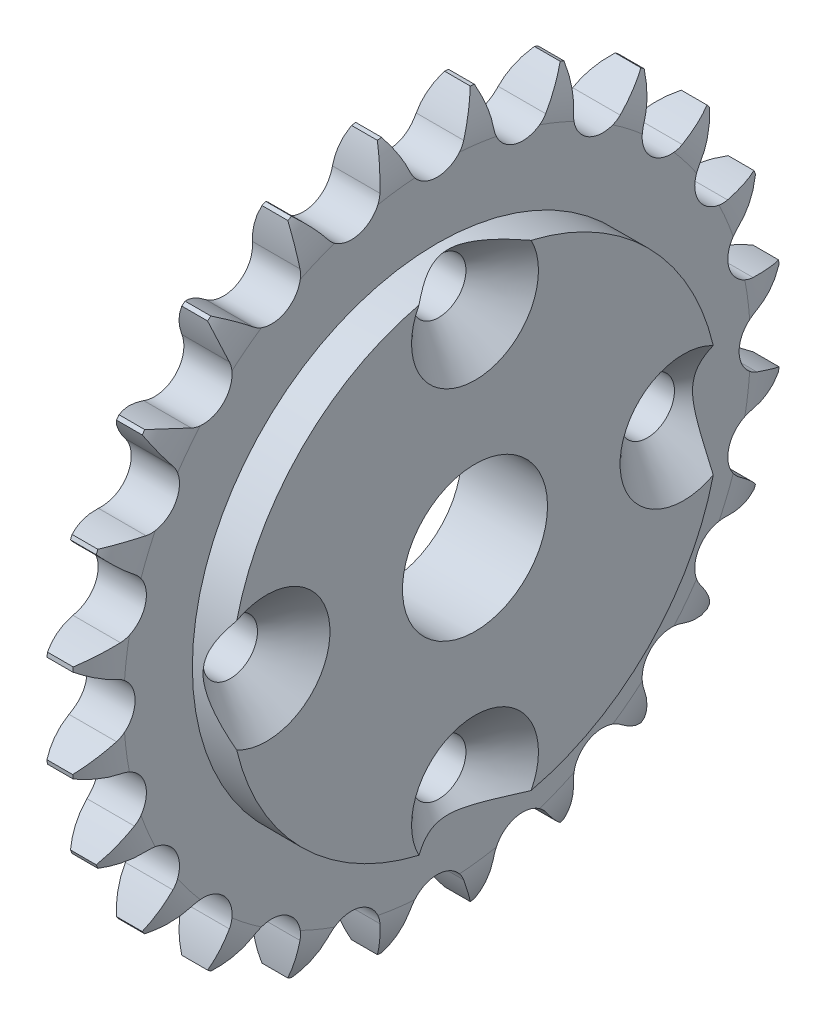
SolidWorks part; units mm, degrees
ref_plane "Plane1" through (0, 0, 0) normal (0, 0, 1) x (1, 0, 0)
ref_plane "Plane2" through (0, 0, 0) normal (0, 1, 0) x (1, 0, 0)
ref_plane "Plane3" through (0, 0, 0) normal (1, 0, 0) x (0, 0, -1)
sketch "Clipboard" plane through (0, 0, 0) normal (0, 1, 0) x (1, 0, 0)
  line L0 (0, 0) -> (8.7015, -3.8742)
  line L1 (-15, 0) -> (100, 0) construction
  line L2 (0, 0) -> (-0.8203, 0.9272)
  line L3 (0, 0) -> (-8.8973, 3.4006)
  line L4 (0, 0) -> (2.832, 1.2609)
  line L5 (0, 0) -> (-46.8476, -17.4728)
  line L6 (0, 0) -> (-4.4098, -2.9753)
  line L7 (-0.8203, 0.9272) -> (44.4955, 22.0583)
  line L8 (-76.2, 38.1) -> (-74.4, 38.1)
  line L9 (-73.3242, 40.7328) -> (-72.926, 40.7699)
  line L10 (-73.4529, 9.1872) -> (-63.2129, 9.1872)
  circle A0 centre (0, 0) radius 3.175
  circle A1 centre (0, 0) radius 31.4996
  circle A2 centre (0, 0) radius 37.5
  dimension "Num_teeth" = 24
  dimension "Thickness" = 5.3196
sketch "BasProSke" plane through (0, 0, 0) normal (0, 1, 0) x (1, 0, 0)
  line L0 (-10, 0) -> (60, 0) construction
  line L1 (0, 0) -> (0, 34.5692)
  line L2 (0, 0) -> (5.3196, 0)
  line L3 (5.3196, 0) -> (5.3196, 34.5692)
  line L4 (4.0816, 39.2651) -> (1.238, 39.2651)
  arc A0 (0, 34.5692) -> (1.238, 39.2651) centre (9.525, 34.5692) cw
  arc A1 (5.3196, 34.5692) -> (4.0816, 39.2651) centre (-4.2054, 34.5692) ccw
  dimension "D1" = 9.525
  dimension "Thickness" = 5.3196
  dimension "Diameter" = 78.5301
revolve "Base-Revolve" add sketch "BasProSke" angle 360 about L0
sketch "TooCutSke" plane through (0, 0, 0) normal (1, 0, 0) x (0, 0, -1)
  line L0 (0, 36.5187) -> (2.9759, 35.3239) construction
  line L1 (0, 0) -> (0, 107) construction
  line L2 (0, 36.5187) -> (-10, 36.5187) construction
  line L3 (0, 36.5187) -> (-2.9759, 35.3239) construction
  arc A0 (2.9759, 35.3239) -> (5.214, 39.4217) centre (21.3614, 27.9423) cw
  arc A1 (2.9759, 35.3239) -> (-2.9759, 35.3239) centre (0, 36.5187) cw
  arc A2 (-2.9759, 35.3239) -> (-5.214, 39.4217) centre (-21.3614, 27.9423) ccw
  arc A3 (5.214, 39.4217) -> (-5.214, 39.4217) centre (0, 0) ccw
extrude "ToothCut" cut sketch "TooCutSke" along normal through all
pattern_circular "TeethCuts" count 24 every 15 about axis through (-10, 0, 0) along (1, 0, 0) of "ToothCut"
sketch "HubNeaOneSke" plane through (0, 0, 0) normal (-1, 0, 0) x (0, 0, 1)
  circle A0 centre (0, 0) radius 31.4996
  dimension "Diameter" = 62.9992
extrude "HubNearOne" [suppressed] add sketch "HubNeaOneSke" along normal blind 44.6809
fillet "HubNearOneFillet" [suppressed] radius 0.4
sketch "HubNeaBotSke" plane through (0, 0, 0) normal (-1, 0, 0) x (0, 0, 1)
  circle A0 centre (0, 0) radius 31.4996
  dimension "Diameter" = 62.9992
extrude "HubNearBoth" [suppressed] add sketch "HubNeaBotSke" along normal blind 22.3405
fillet "HubNearBothFillet" [suppressed] radius 0.4
ref_plane "FarPln" through (5.3196, 0, 0) normal (1, 0, 0) x (0, 0, -1)
sketch "HubFarSke" plane through (5.3196, 0, 0) normal (1, 0, 0) x (0, 0, -1)
  circle A0 centre (0, 0) radius 31.4996
  dimension "Diameter" = 62.9992
extrude "HubFar" [suppressed] add sketch "HubFarSke" along normal blind 22.3405
fillet "HubFarFillet" [suppressed] radius 0.4
sketch "BorSke" plane through (0, 0, 0) normal (1, 0, 0) x (0, 0, -1)
  circle A0 centre (0, 0) radius 5
  dimension "Diameter" = 10
extrude "Bore" cut sketch "BorSke" along normal mid plane 100.001
sketch "KeySke" plane through (0, 0, 0) normal (1, 0, 0) x (0, 0, -1)
  line L0 (-2, 0) -> (-2, 6.8)
  line L1 (-2, 6.8) -> (2, 6.8)
  line L2 (2, 6.8) -> (2, 0)
  line L3 (0, 0) -> (0, 34) construction
  line L4 (-2, 0) -> (2, 0)
  dimension "Width" = 4
extrude "Keyway" [suppressed] cut sketch "KeySke" along normal mid plane 100.001
pattern_circular "Keyway2" [suppressed] count 2 every 90 about axis through (-10, 0, 0) along (1, 0, 0)
sketch "Sketch1" plane through (5.3196, 0, 0) normal (1, 0, 0) x (0, 0, -1)
  circle A0 centre (0, 0) radius 27
  circle A1 centre (0, 0) radius 6
  dimension "D1" = 54
  dimension "D2" = 12
extrude "Boss-Extrude1" add sketch "Sketch1" along normal offset from surface (22.6804 mm away) 28 up to face at (0, 0, -5)
sketch "Sketch2" plane through (28, 0, 0) normal (1, 0, 0) x (0, 0, -1)
  circle A0 centre (0, 0) radius 39.4959
extrude "trim boss" cut sketch "Sketch2" against normal blind 18.5
sketch "Sketch3" plane through (9.5, 0, 0) normal (1, 0, 0) x (0, 0, -1)
  circle A0 centre (0, 0) radius 8
  dimension "D1" = 16
extrude "bore centre" cut sketch "Sketch3" against normal blind 20
sketch "Sketch4" plane through (0, 0, 0) normal (-1, 0, 0) x (0, 0, 1)
  circle A0 centre (0, 23) radius 3
  circle A1 centre (23, 0) radius 3
  circle A2 centre (0, -23) radius 3
  circle A3 centre (-23, 0) radius 3
  circle A4 centre (0, 0) radius 23 construction
  dimension "D1" = 6
  dimension "D2" = 46
extrude "Cut-Extrude3" cut sketch "Sketch4" against normal blind 20
chamfer "Chamfer1" distance 4 angle 45 4 edges at (9.5, 0, -26) (9.5, -23, -3) (9.5, 0, 20) (9.5, 23, -3)
equation "' \"Pitch@Clipboard\" = 12.7"
equation "' \"Num_strands@Clipboard\" = 1"
equation "' \"Num_teeth@Clipboard\" = 9"
equation "' \"Hub_dia@Clipboard\" = 50"
equation "' \"Overall_len@Clipboard\" = 3"
equation "' \"Diameter@BorSke\" = 12"
equation "' \"T_dim@Clipboard\" = 1"
equation "' \"Width@KeySke\" = 2"
equation "' \"Dr@Clipboard\" = 8.51"
equation "' \"Face_width@Clipboard\" = 7.2"
equation "' \"Side_radius@Clipboard\" = 12.7"
equation "' \"Side_relief@Clipboard\" = 1.27"
equation "' \"Transv_pitch@Clipboard\" = 13.92"
equation "' \"Show_teeth@Clipboard\" = 9"
equation "' \"Fillet_rad@Clipboard\" = 0.6"
equation "' \"Plate_wid@Clipboard\" = 11.8"
equation "\"Num_teeth@Clipboard\" = int( \"Num_teeth@Clipboard\" )"
equation "\"Num_teeth@Clipboard\" = ((sgn( \"Num_teeth@Clipboard\" - 5.0)+1)*( \"Num_teeth@Clipboard\" - 5.0))/2 +5.0"
equation "\"Num_teeth@Clipboard\" = ((sgn( \"Num_teeth@Clipboard\" - 200.0)-1)*( \"Num_teeth@Clipboard\" - 200.0))/-2 +200.0"
equation "\"MHD@Clipboard\" = \"Pitch@Clipboard\" * (1.0 / tan(3.14159265 / \"Num_teeth@Clipboard\" )) - 1.04 * \"Plate_wid@Clipboard\" - 0.76"
equation "\"Thickness@Clipboard\"  = \"Face_width@Clipboard\" + (\"Num_strands@Clipboard\" - 1) * \"Transv_pitch@Clipboard\""
equation "\"OAL@Clipboard\" = \"Thickness@Clipboard\" + 2 * \"Fillet_rad@Clipboard\" + 1"
equation "\"MHD@Clipboard\" = ((sgn( \"MHD@Clipboard\" - \"Hub_dia@Clipboard\" )-1)*( \"MHD@Clipboard\" - \"Hub_dia@Clipboard\" ))/-2+ \"Hub_dia@Clipboard\""
equation "\"OAL@Clipboard\" = ((sgn( \"OAL@Clipboard\" - \"Overall_len@Clipboard\" )+1)*( \"OAL@Clipboard\" - \"Overall_len@Clipboard\" ))/2 + \"Overall_len@Clipboard\" + 0.0005"
equation "\"Num_teeth@TeethCuts\" = int( \"Show_teeth@Clipboard\" ) + 1"
equation "\"Num_teeth@TeethCuts\" = ((sgn( \"Num_teeth@TeethCuts\" - \"Num_teeth@Clipboard\" )-1)*( \"Num_teeth@TeethCuts\" - \"Num_teeth@Clipboard\" ))/-2+ \"Num_teeth@Clipboard\""
equation "\"Num_teeth@TeethCuts\" = ((sgn( \"Num_teeth@TeethCuts\" - 2.0)+1)*( \"Num_teeth@TeethCuts\" - 2.0))/2 +2.0"
equation "\"Angle@TeethCuts\" = 360.0 / \"Num_teeth@Clipboard\""
equation "\"Seat_radius@TooCutSke\" = ( \"Pitch@Clipboard\" / 2.0) / sin(3.14159265 / \"Num_teeth@Clipboard\" ) - \"Dr@Clipboard\" / 2.0 + \"Dr@Clipboard\" * 0.505"
equation "\"R1@TooCutSke\"  = \"Dr@Clipboard\" * 0.505"
equation "\"X@TooCutSke\" = 140.0 - (90.0 / \"Num_teeth@Clipboard\")"
equation "\"R2@TooCutSke\" = 0.12 * \"Dr@Clipboard\" * ( \"Num_teeth@Clipboard\" + 2.0)"
equation "\"Overcut@TooCutSke\" = 0.5 + 0.625 * \"Pitch@Clipboard\" - 0.5 * \"Dr@Clipboard\"  +  \"Pitch@Clipboard\" / 2.0 / sin(3.14159265 / \"Num_teeth@Clipboard\" )"
equation "\"Diameter@BasProSke\" = 2.0 * ( 0.625 * \"Pitch@Clipboard\" - 0.5 * \"Dr@Clipboard\"  +  \"Pitch@Clipboard\" / 2.0 / sin(3.14159265 / \"Num_teeth@Clipboard\" ))"
equation "\"Thickness@BasProSke\"  = \"Thickness@Clipboard\""
equation "\"G1@BasProSke\" =  \"Side_relief@Clipboard\""
equation "\"G2@BasProSke\" =  \"Side_relief@Clipboard\""
equation "\"D1@BasProSke\" =  \"Side_radius@Clipboard\""
equation "\"Diameter@HubNeaOneSke\" = \"MHD@Clipboard\""
equation "\"Length@HubNearOne\" = \"OAL@Clipboard\" - \"Thickness@BasProSke\""
equation "\"Diameter@HubNeaBotSke\" = \"MHD@Clipboard\""
equation "\"Length@HubNearBoth\" = ( \"OAL@Clipboard\" - \"Thickness@BasProSke\" ) / 2.0"
equation "\"D1@HubNearOneFillet\" = \"Fillet_rad@Clipboard\""
equation "\"D1@HubNearBothFillet\" = \"Fillet_rad@Clipboard\""
equation "\"Thickness@FarPln\" = \"Thickness@BasProSke\""
equation "\"Diameter@HubFarSke\" = \"MHD@Clipboard\""
equation "\"Length@HubFar\" = ( \"OAL@Clipboard\" - \"Thickness@BasProSke\" ) / 2.0"
equation "\"D1@HubFarFillet\" = \"Fillet_rad@Clipboard\""
equation "\"D1@Bore\" = \"OAL@Clipboard\" * 2.0"
equation "\"D1@Keyway\" = \"OAL@Clipboard\" * 2.0"
equation "\"Offset@KeySke\" = \"T_dim@Clipboard\" + \"Diameter@BorSke\" / 2.0"
